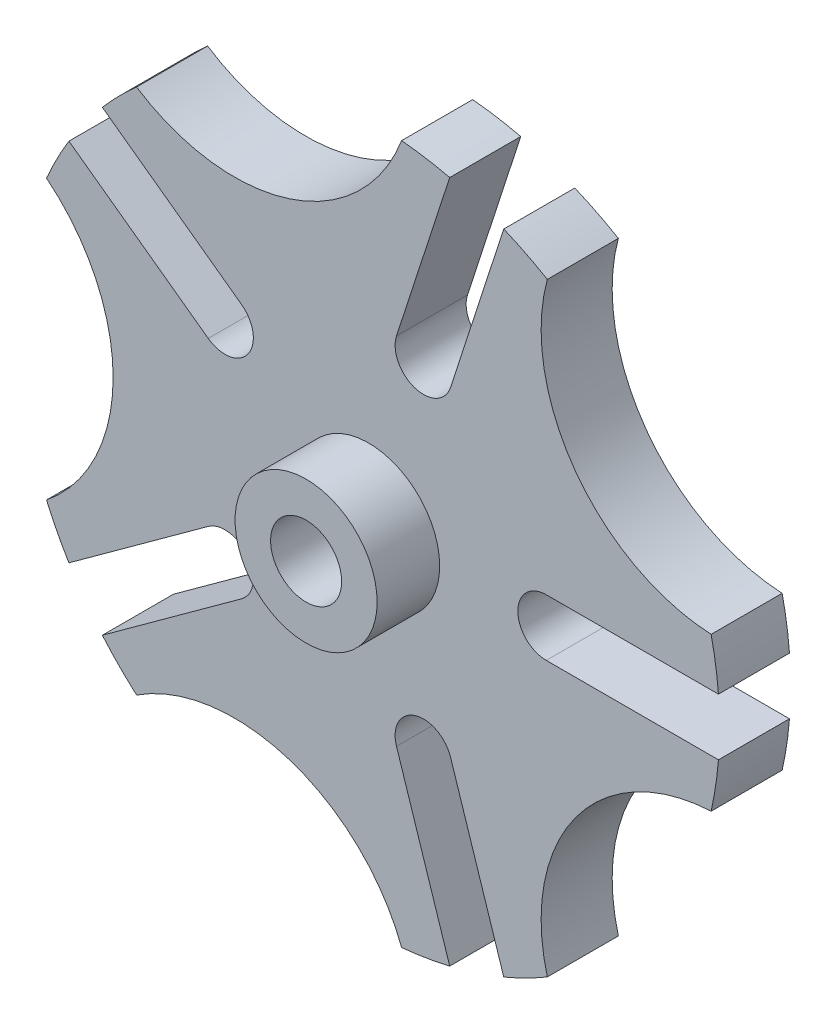
SolidWorks part; units mm, degrees
material "Chromium Copper, UNS C18200"
ref_plane "Front Plane" through (0, 0, 0) normal (0, 0, 1) x (1, 0, 0)
ref_plane "Top Plane" through (0, 0, 0) normal (0, 1, 0) x (1, 0, 0)
ref_plane "Right Plane" through (0, 0, 0) normal (1, 0, 0) x (0, 0, -1)
sketch "Sketch1" plane through (0, 0, 0) normal (0, 0, 1) x (1, 0, 0)
  line L0 (0, 36.9358) -> (0, -36.9358) construction
  line L1 (-34.8045, 0) -> (38.3706, 0) construction
  line L2 (0, 0) -> (4.8191, 14.8316) construction
  line L3 (0, 0) -> (-0.1957, 0) construction
  line L4 (0, 0) -> (31.4195, 22.8276) construction
  line L5 (15.875, 2.54) -> (31.266, 2.54)
  line L6 (7.2508, 14.1224) -> (12.0699, 28.954)
  line L7 (2.4349, 15.6872) -> (7.254, 30.5187)
  line L8 (15.875, -2.54) -> (31.266, -2.54)
  line L9 (7.3213, -14.3131) -> (12.0774, -28.9508)
  line L10 (2.49, -15.8829) -> (7.246, -30.5206)
  line L11 (15.6718, 2.5319) -> (31.2667, 2.5319)
  line L12 (15.6718, -2.5319) -> (31.2667, -2.5319)
  line L13 (-11.3502, -11.386) -> (-23.8017, -20.4326)
  line L14 (-14.3361, -7.2762) -> (-26.7877, -16.3228)
  line L15 (7.2508, -14.1224) -> (12.0699, -28.954)
  line L16 (2.4349, -15.6872) -> (7.254, -30.5187)
  line L17 (-14.3361, 7.2762) -> (-26.7877, 16.3228)
  line L18 (-11.3502, 11.386) -> (-23.8017, 20.4326)
  line L19 (-11.1906, -11.26) -> (-23.8071, -20.4264)
  line L20 (-14.1669, -7.1633) -> (-26.7834, -16.3298)
  line L21 (2.49, 15.8829) -> (7.246, 30.5206)
  line L22 (7.3213, 14.3131) -> (12.0774, 28.9508)
  line L23 (-14.1669, 7.1633) -> (-26.7834, 16.3298)
  line L24 (-11.1906, 11.26) -> (-23.8071, 20.4264)
  arc A0 (15.9708, 26.9991) -> (12.0699, 28.954) centre (0, 0) ccw
  circle A1 centre (0, 0) radius 15.875 construction
  arc A2 (15.875, 2.54) -> (15.875, -2.54) centre (15.875, 0) ccw
  arc A3 (2.5605, 16.0737) -> (7.3764, 14.5089) centre (4.9056, 15.098) ccw
  arc A4 (15.9708, 26.9991) -> (30.6129, 6.8459) centre (31.4195, 22.8276) ccw
  arc A5 (7.254, 30.5187) -> (2.949, 31.2301) centre (0, 0) ccw
  arc A6 (31.266, 2.54) -> (30.6129, 6.8459) centre (0, 0) ccw
  arc A7 (16.0782, 2.5319) -> (16.0782, -2.5319) centre (15.875, 0) ccw
  arc A8 (7.3213, -14.3131) -> (2.49, -15.8829) centre (4.9056, -15.098) ccw
  arc A9 (30.6129, -6.8459) -> (15.9708, -26.9991) centre (31.4195, -22.8276) ccw
  arc A10 (7.3764, -14.5089) -> (2.5605, -16.0737) centre (4.9056, -15.098) ccw
  arc A11 (-11.3502, -11.386) -> (-14.3361, -7.2762) centre (-12.8431, -9.3311) ccw
  arc A12 (2.949, -31.2301) -> (-20.7424, -23.5323) centre (-12.0012, -36.9358) ccw
  arc A13 (-11.5193, -11.4988) -> (-14.4957, -7.4022) centre (-12.8431, -9.3311) ccw
  arc A14 (-14.3361, 7.2762) -> (-11.3502, 11.386) centre (-12.8431, 9.3311) ccw
  arc A15 (-28.7903, -12.4553) -> (-28.7903, 12.4553) centre (-38.8366, 0) ccw
  arc A16 (-14.4957, 7.4022) -> (-11.5193, 11.4988) centre (-12.8431, 9.3311) ccw
  arc A17 (2.49, 15.8829) -> (7.3213, 14.3131) centre (4.9056, 15.098) ccw
  arc A18 (-20.7424, 23.5323) -> (2.949, 31.2301) centre (-12.0012, 36.9358) ccw
  arc A19 (-26.7834, 16.3298) -> (-28.7903, 12.4553) centre (0, 0) ccw
  arc A20 (12.0699, -28.954) -> (15.9708, -26.9991) centre (0, 0) ccw
  arc A21 (2.949, -31.2301) -> (7.254, -30.5187) centre (0, 0) ccw
  arc A22 (30.6129, -6.8459) -> (31.266, -2.54) centre (0, 0) ccw
  arc A23 (-23.8071, -20.4264) -> (-20.7424, -23.5323) centre (0, 0) ccw
  arc A24 (-28.7903, -12.4553) -> (-26.7834, -16.3298) centre (0, 0) ccw
  arc A25 (-20.7424, 23.5323) -> (-23.8071, 20.4264) centre (0, 0) ccw
  point P87 (0, 0)
  dimension "D1" = 62.738
  dimension "D2" = 31.75
  dimension "D4" = 36
  dimension "D5" = 5.08
  dimension "D7" = 16.002
  dimension "D3" = 72
  dimension "D6" = 38.8366
  dimension "D8" = 5
extrude "Boss-Extrude1" add sketch "Sketch1" along normal blind 6.35 contours A18 A25 L18 A14 L17 A19 A15 A24 L14 A11 L13 A23 A12 A21 L10 A8 L9 A20 A9 A22 L8 A2 L5 A6 A4 A0 L22 A3 L21 A5 region at (0, 0, 0)
sketch "Sketch2" plane through (0, 0, 6.35) normal (0, 0, 1) x (1, 0, 0)
  circle A0 centre (0, 0) radius 6.35
  circle A1 centre (0, 0) radius 3.175
  dimension "D1" = 12.7
  dimension "D2" = 6.35
extrude "Boss-Extrude2" add sketch "Sketch2" along normal blind 5.588
extrude "Cut-Extrude1" cut sketch "Sketch2<2>" against normal through all body kept at (-14.3361, -7.2762, 0) body kept at (6.35, 0, 11.938)
sketch "Sketch2<2>" plane through (0, 0, 6.35) normal (0, 0, 1) x (1, 0, 0) same geometry as "Sketch2"
